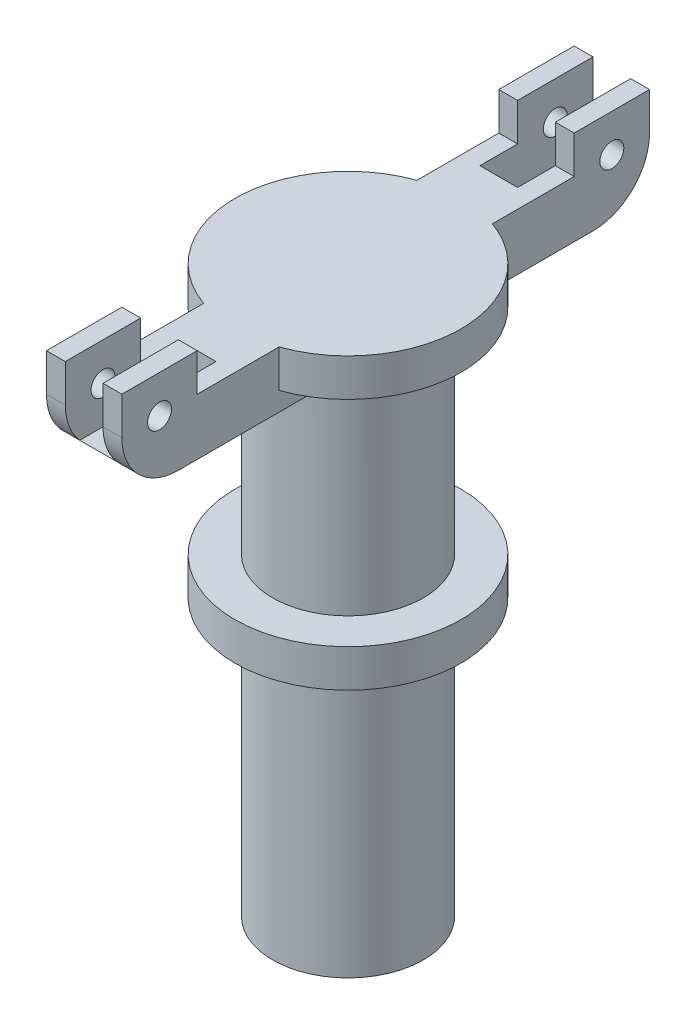
SolidWorks part; units mm, degrees
ref_plane "Front Plane" through (0, 0, 0) normal (0, 0, 1) x (1, 0, 0)
ref_plane "Top Plane" through (0, 0, 0) normal (0, 1, 0) x (1, 0, 0)
ref_plane "Right Plane" through (0, 0, 0) normal (1, 0, 0) x (0, 0, -1)
sketch "Sketch1" plane through (0, 0, 0) normal (0, 1, 0) x (1, 0, 0)
  line L0 (0, -430.4848) -> (0, 21093.7534) construction
  line L1 (-430.4848, 0) -> (21093.7534, 0) construction
  circle A0 centre (0, 0) radius 30
  dimension "D1" = 60
extrude "Boss-Extrude1" add sketch "Sketch1" along normal mid plane 150
sketch "Sketch2" plane through (0, 0, 0) normal (1, 0, 0) x (0, 0, -1)
  line L1 (30, 65) -> (20, 65)
  line L3 (30, -1.81) -> (20, -1.81)
  line L4 (20, 65) -> (20, 8.19)
  line L5 (0, -1000) -> (0, 49000) construction
  line L14 (30, 65) -> (30, 8.19)
  line L18 (30, 75) -> (-30, 75) construction
  line L19 (30, -75) -> (30, 75) construction
  line L21 (20, 8.19) -> (30, 8.19)
  line L22 (20, -1.81) -> (20, -75)
  line L23 (20, -75) -> (30, -75)
  line L24 (30, -1.81) -> (30, -75)
  dimension "D1" = 10
  dimension "D2" = 10
  dimension "D3" = 56.81
  dimension "D4" = 20
revolve "Cut-Revolve1" cut sketch "Sketch2" angle 360 about L5
sketch "Sketch3" plane through (0, 0, 0) normal (1, 0, 0) x (0, 0, -1)
  line L17 (0, 75) -> (0, 60)
  line L21 (70, 60) -> (70, 85)
  line L22 (70, 85) -> (50, 85)
  line L23 (50, 85) -> (50, 75)
  line L24 (50, 75) -> (0, 75)
  line L25 (70, 60) -> (0, 60)
  line L27 (0, -1000) -> (0, 49000) construction
  line L28 (30, 75) -> (-30, 75) construction
  circle A1 centre (60, 75) radius 3.175
  dimension "D8" = 10
  dimension "D2" = 20
  dimension "D3" = 25
  dimension "D9" = 10
  dimension "D11" = 60
extrude "Boss-Extrude2" add sketch "Sketch3" along normal mid plane 20
sketch "Sketch5" plane through (0, 0, -70) normal (0, 0, -1) x (-1, 0, 0)
  line L0 (-10, 85) -> (10, 85) construction
  line L1 (-5, 85) -> (5, 85)
  line L2 (-5, 85) -> (-5, 65)
  line L3 (-5, 65) -> (5, 65)
  line L4 (5, 85) -> (5, 65)
  line L5 (0, -905) -> (0, 49095) construction
  point P9 (0, 85)
  point P12 (0, 85)
  dimension "D1" = 10
  dimension "D2" = 20
extrude "Cut-Extrude2" cut sketch "Sketch5" against normal blind 30
fillet "Fillet1" radius 15 1 edges at (0, 60, -70)
mirror "Mirror1" about plane through (0, 0, 0) normal (0, 0, 1) of "Fillet1", "Cut-Extrude2", "Boss-Extrude2"
